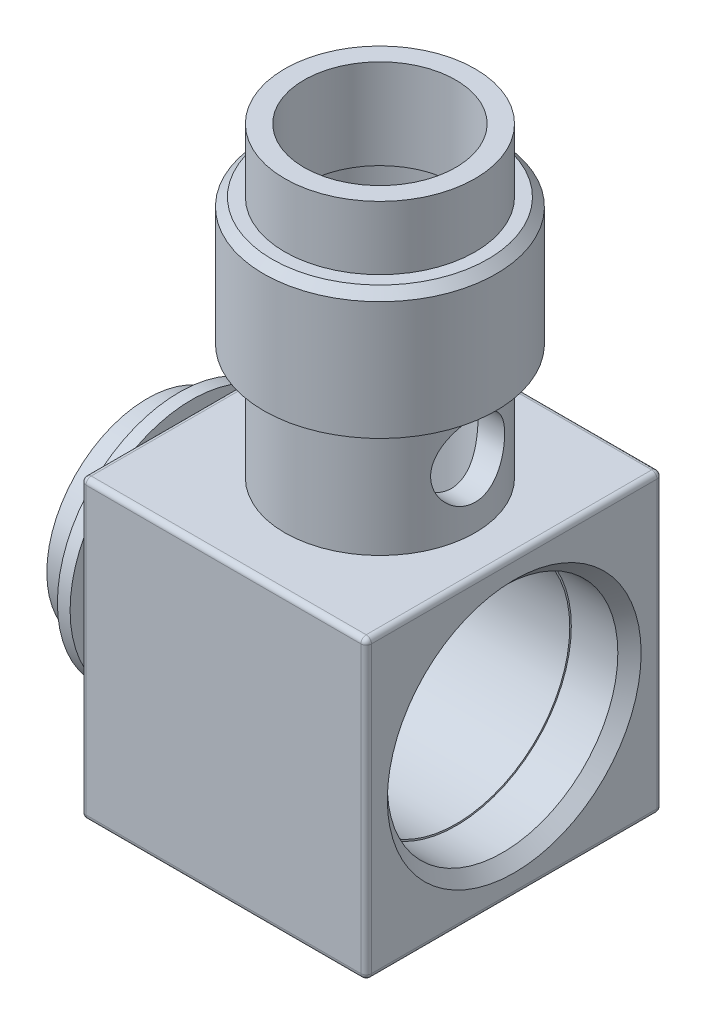
SolidWorks part; units mm, degrees
material "Сталь"
ref_plane "Спереди" through (0, 0, 0) normal (0, 0, 1) x (1, 0, 0)
ref_plane "Сверху" through (0, 0, 0) normal (0, 1, 0) x (1, 0, 0)
ref_plane "Справа" through (0, 0, 0) normal (1, 0, 0) x (0, 0, -1)
sketch "Эскиз1" plane through (0, 0, 0) normal (0, 0, 1) x (1, 0, 0)
  line L0 (0, 0) -> (53.6101, 0) construction
  line L1 (0, -7) -> (11.6, -7)
  line L2 (0, -7) -> (0, -9.5)
  line L3 (0, -9.5) -> (3, -9.5)
  line L4 (3, -9.5) -> (3, -11.5)
  line L5 (3, -11.5) -> (4.2, -11.5)
  line L6 (4.2, -11.5) -> (4.2, -9.5)
  line L7 (4.2, -9.5) -> (7.7, -9.5)
  line L8 (7.7, -9.5) -> (7.7, -14)
  line L9 (7.7, -14) -> (34.7, -14)
  line L10 (34.7, -14) -> (34.7, -10.5)
  line L11 (34.7, -10.5) -> (11.6, -10.5) construction
  line L12 (11.6, -10.5) -> (11.6, -7) construction
  line L13 (11.6, -7) -> (11.6, 0)
  line L14 (11.6, 0) -> (34.7, 0)
  line L15 (34.7, 0) -> (34.7, -10.5)
  dimension "D1" = 11.6
  dimension "D2" = 7
  dimension "D3" = 9.5
  dimension "D4" = 3
  dimension "D5" = 2
  dimension "D6" = 1.2
  dimension "D7" = 14
  dimension "D8" = 27
  dimension "D9" = 3.5
  dimension "D10" = 3.5
revolve "Повернуть1" add sketch "Эскиз1" angle 360 about L0
sketch "Эскиз2" plane through (0, 0, 0) normal (0, 1, 0) x (1, 0, 0)
  circle A0 centre (22, 0) radius 9
  dimension "D1" = 18
  dimension "D2" = 22
extrude "Бобышка-Вытянуть1" add sketch "Эскиз2" along normal blind 25
sketch "Эскиз3" plane through (0, 25, 0) normal (0, 1, 0) x (1, 0, 0)
  circle A0 centre (22, 0) radius 11
  dimension "D1" = 22
extrude "Бобышка-Вытянуть2" add sketch "Эскиз3" along normal blind 12
cosmetic thread "Условное изображение резьбы1" parameters "D2"=20.344
sketch "Эскиз4" plane through (0, 37, 0) normal (0, 1, 0) x (1, 0, 0)
  circle A0 centre (22, 0) radius 9
  dimension "D1" = 18
extrude "Бобышка-Вытянуть3" add sketch "Эскиз4" along normal blind 6
sketch "Эскиз5" plane through (34.7, 0, 0) normal (1, 0, 0) x (0, 0, -1)
  circle A0 centre (0, 0) radius 10.75
  dimension "D1" = 21.5
extrude "Вырез-Вытянуть1" cut sketch "Эскиз5" against normal up to surface (23.1 mm away) up to face at (11.6, 0, 7)
sketch "Эскиз6" plane through (0, 43, 0) normal (0, 1, 0) x (1, 0, 0)
  circle A0 centre (22, 0) radius 8.5
  dimension "D1" = 17
extrude "Вырез-Вытянуть2" cut sketch "Эскиз6" against normal blind 7 from offset 8.5 offset against normal yes
sketch "Эскиз8" plane through (0, 27.5, 0) normal (0, 1, 0) x (1, 0, 0)
  circle A0 centre (22, 0) radius 6.75
  dimension "D1" = 13.5
extrude "Вырез-Вытянуть3" cut sketch "Эскиз8" against normal up to next
sketch "Эскиз9" plane through (0, 0, 0) normal (1, 0, 0) x (0, 0, -1)
  circle A0 centre (0, 20) radius 3.5
  dimension "D2" = 7
  dimension "D1" = 20
extrude "Вырез-Вытянуть4" cut sketch "Эскиз9" along normal through all
sketch "Эскиз10" plane through (34.7, 0, 0) normal (1, 0, 0) x (0, 0, -1)
  circle A0 centre (0, 0) radius 10.75 construction
  circle A1 centre (0, 0) radius 10.75
extrude "Бобышка-Вытянуть4" add sketch "Эскиз10" against normal blind 5.95
chamfer "Фаска1" distance 0.8 angle 45 1 edges at (22, 37, 11)
sketch "Эскиз12" plane through (34.7, 0, 0) normal (1, 0, 0) x (0, 0, -1)
  line L1 (-14, -14) -> (14, -14)
  line L2 (-14, -14) -> (-14, 14)
  line L3 (-14, 14) -> (14, 14)
  line L4 (14, -14) -> (14, 14)
  line L5 (-14, -14) -> (14, 14) construction
  line L6 (-14, 14) -> (14, -14) construction
  circle A0 centre (0, 0) radius 14 construction
  circle A3 centre (0, 0) radius 13
  circle A4 centre (0, 0) radius 13
  point P0 (0, 0)
  dimension "D1" = 1
extrude "Бобышка-Вытянуть5" add sketch "Эскиз12" against normal up to surface (27 mm away) up to face at (7.7, 0, 14)
sketch "Эскиз13" plane through (0, 14, 0) normal (0, 1, 0) x (1, 0, 0)
  circle A1 centre (22, 0) radius 6.75
  circle A2 centre (22, 0) radius 6.75
  dimension "D1" = 0
extrude "Вырез-Вытянуть5" cut sketch "Эскиз13" against normal up to next
sketch "Эскиз14" plane through (0, 43, 0) normal (0, 1, 0) x (1, 0, 0)
  circle A0 centre (22, 0) radius 7.172
  dimension "D1" = 14.344
extrude "Вырез-Вытянуть6" cut sketch "Эскиз14" against normal up to next
cosmetic thread "Условное изображение резьбы2" parameters "D2"=16
sketch "Эскиз16" plane through (34.7, 0, 0) normal (1, 0, 0) x (0, 0, -1)
  circle A0 centre (0, 0) radius 10.8985
  dimension "D1" = 21.797
extrude "Вырез-Вытянуть7" cut sketch "Эскиз16" against normal blind 5.5
cosmetic thread "Условное изображение резьбы3" parameters "D1"=5.5, "D2"=24
chamfer "Фаска3" distance 1.1015 angle 45 1 edges at (34.7, 0, -10.8985)
sketch "Эскиз18" plane through (28.75, 0, 0) normal (-1, 0, 0) x (0, 0, 1)
  circle A1 centre (0, 0) radius 10.75
  circle A2 centre (0, 0) radius 10.75
  dimension "D1" = 0
extrude "Вырез-Вытянуть11" cut sketch "Эскиз18" against normal up to next
fillet "Скругление1" radius 0.5 12 edges at (7.7, 0, -14) (34.7, 0, -14) (21.2, 14, -14) (7.7, -14, 0) (34.7, -14, 0) (21.2, -14, -14) (21.2, -14, 14) (7.7, 0, 14) (21.2, 14, 14) (34.7, 0, 14) (34.7, 14, 0) (7.7, 14, 0)
